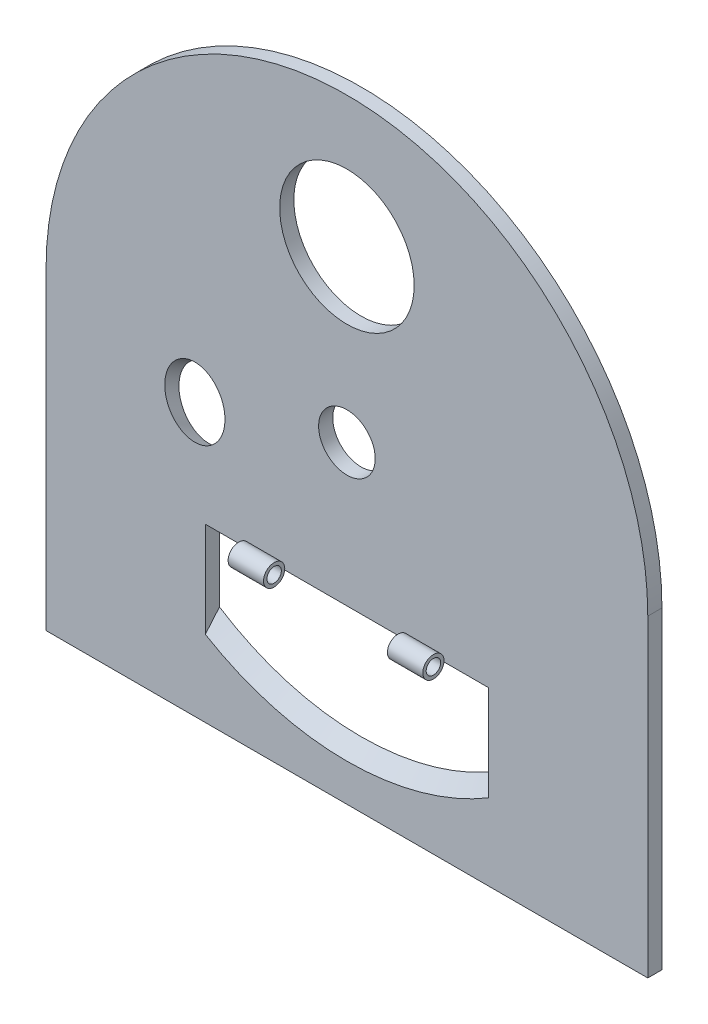
SolidWorks part; units mm, degrees
ref_plane "Front Plane" through (0, 0, 0) normal (0, 0, 1) x (1, 0, 0)
ref_plane "Top Plane" through (0, 0, 0) normal (0, 1, 0) x (1, 0, 0)
ref_plane "Right Plane" through (0, 0, 0) normal (1, 0, 0) x (0, 0, -1)
sketch "Sketch1" plane through (0, 0, 0) normal (0, 0, 1) x (1, 0, 0)
  line L1 (170, 0) -> (170, -177.0771)
  line L2 (-170, 0) -> (-170, -177.0771)
  line L3 (0, 0) -> (0, -184.5757) construction
  line L4 (-80, -80) -> (-80, -124.5151)
  line L5 (80, -80) -> (80, -124.5151)
  line L6 (-80, -80) -> (80, -80)
  line L7 (80, 0) -> (80, -184.5757) construction
  line L8 (-80, 0) -> (-80, -184.5757) construction
  line L9 (-170, -177.0771) -> (170, -177.0771)
  arc A0 (170, 0) -> (-170, 0) centre (0, 0) ccw
  circle A2 centre (0, 0) radius 16
  circle A3 centre (0, 95.8001) radius 38
  circle A4 centre (-85.9187, -23.2506) radius 10
  arc A6 (-80, -124.5151) -> (80, -124.5151) centre (0, 0) ccw
  dimension "D1" = 340
  dimension "D5" = 32
  dimension "D6" = 76
  dimension "D7" = 20
  dimension "D8" = 296
  dimension "D4" = 80
  dimension "D2" = 80
  dimension "D3" = 80
extrude "Boss-Extrude1" add sketch "Sketch1" along normal blind 8
chamfer "Chamfer1" distance 8 angle 45 1 edges at (0, -148, 8)
sketch "Sketch2" plane through (0, 0, 8) normal (0, 0, 1) x (1, 0, 0)
  line L0 (-75.9187, -23.2506) -> (-95.9187, -23.2506) construction
  circle A0 centre (-85.9187, -23.2506) radius 10 construction
ref_plane "Plane1" through (0, -2.3486, -4.0678) normal (0, 0.5, 0.866) x (-1, 0, 0)
sketch "Sketch3" plane through (0, -2.3486, -4.0678) normal (0, 0.5, 0.866) x (-1, 0, 0)
  line L0 (75.9187, 24.1356) -> (95.9187, 24.1356) construction
  circle A0 centre (85.9187, 24.1356) radius 17
  dimension "D1" = 34
extrude "Cut-Extrude1" cut sketch "Sketch3" against normal through all and the other way through all
ref_plane "Plane2" through (55, 0, 0) normal (-1, 0, 0) x (0, 0, 1)
ref_plane "Plane3" through (0, 0, 0) normal (1, 0, 0) x (0, 0, -1)
sketch "Sketch4" plane through (55, 0, 0) normal (-1, 0, 0) x (0, 0, 1)
  circle A0 centre (14.1224, -79.2179) radius 4.08
  circle A1 centre (14.1224, -79.2179) radius 6
extrude "Boss-Extrude2" add sketch "Sketch4" along normal blind 20 separate body
mirror "Mirror2" about plane through (0, 0, 0) normal (1, 0, 0) of bodies 105
sketch "Sketch5" plane through (0, 0, 8) normal (0, 0, 1) x (1, 0, 0)
  circle A0 centre (0, 0) radius 26
  dimension "D1" = 52
